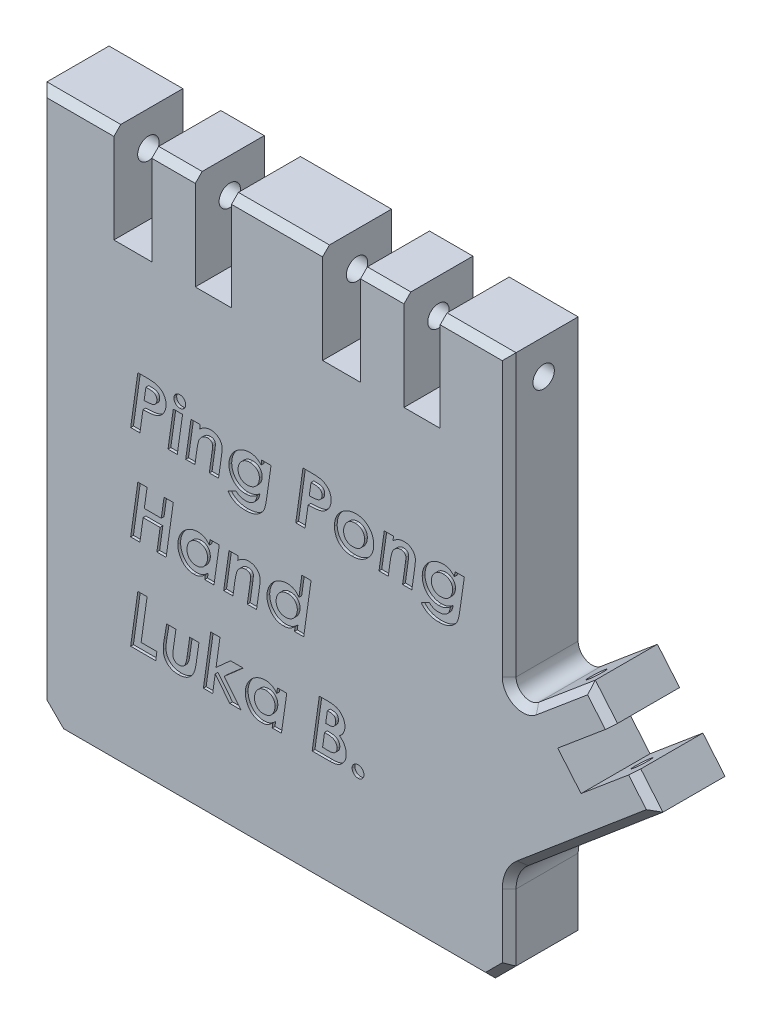
SolidWorks part; units mm, degrees
ref_plane "Plan de face" through (0, 0, 0) normal (0, 0, 1) x (1, 0, 0)
ref_plane "Plan de dessus" through (0, 0, 0) normal (0, 1, 0) x (1, 0, 0)
ref_plane "Plan de droite" through (0, 0, 0) normal (1, 0, 0) x (0, 0, -1)
sketch "Esquisse1" plane through (0, 0, 0) normal (0, 0, 1) x (1, 0, 0)
  line L1 (-34, -40) -> (34, -40)
  line L2 (-34, -40) -> (-34, 40)
  line L3 (-34, 40) -> (34, 40)
  line L4 (34, -40) -> (34, 40)
  line L5 (-34, -40) -> (34, 40) construction
  line L6 (-34, 40) -> (34, -40) construction
  point P0 (0, 0)
  dimension "D1" = 68
  dimension "D2" = 80
extrude "Boss.-Extru.1" add sketch "Esquisse1" along normal blind 10
sketch "Esquisse2" plane through (0, 0, 10) normal (0, 0, 1) x (1, 0, 0)
  line L0 (34, 40) -> (-34, 40) construction
  line L1 (18.75, 40) -> (24, 40)
  line L2 (18.75, 40) -> (18.75, 26)
  line L3 (18.75, 26) -> (24, 26)
  line L4 (24, 40) -> (24, 26)
  line L5 (34, -40) -> (34, 40) construction
  line L10 (-11.5, 40) -> (-6.25, 40)
  line L11 (-11.5, 40) -> (-11.5, 26)
  line L12 (-11.5, 26) -> (-6.25, 26)
  line L13 (-6.25, 40) -> (-6.25, 26)
  dimension "D1" = 5.25
  dimension "D2" = 10
  dimension "D3" = 14
  dimension "D4" = 25
extrude "Enlèv. mat.-Extru.1" cut sketch "Esquisse2" against normal blind 10
sketch "Esquisse3" plane through (34, 0, 0) normal (1, 0, 0) x (0, 0, -1)
  line L0 (-10, 40) -> (0, 40) construction
  circle A0 centre (-5, 35) radius 1.55
  point P4 (-5, 40)
  dimension "D1" = 3.1
  dimension "D2" = 5
extrude "Enlèv. mat.-Extru.2" cut sketch "Esquisse3" against normal through all
sketch "Esquisse8" plane through (0, 0, 10) normal (0, 0, 1) x (1, 0, 0)
  line L0 (34, -5) -> (45.4907, 4.6418)
  line L1 (34, -40) -> (34, 40) construction
  line L2 (45.4907, 4.6418) -> (48.7046, 0.8116)
  line L3 (48.7046, 0.8116) -> (41.0442, -5.6163)
  line L4 (41.0442, -5.6163) -> (44.4188, -9.638)
  line L5 (44.4188, -9.638) -> (52.0792, -3.2101)
  line L6 (52.0792, -3.2101) -> (55.2932, -7.0404)
  line L7 (55.2932, -7.0404) -> (34, -25)
  line L8 (34, -25) -> (34, -5)
  line L9 (-34, -40) -> (34, -40) construction
  dimension "D1" = 5.25
  dimension "D2" = 5
  dimension "D3" = 5
  dimension "D4" = 15
  dimension "D5" = 50
  dimension "D6" = 15
  dimension "D7" = 20
  dimension "D8" = 10
extrude "Boss.-Extru.3" add sketch "Esquisse8" against normal blind 10
sketch "Esquisse9" plane through (19.7239, -23.5061, 0) normal (0.6428, -0.766, 0) x (0.766, 0.6428, 0)
  line L0 (37.8316, 0) -> (37.8316, 10) construction
  circle A0 centre (32.8316, 5) radius 1.25
  point P4 (37.8316, 5)
  dimension "D1" = 2.5
  dimension "D2" = 5
extrude "Enlèv. mat.-Extru.6" cut sketch "Esquisse9" against normal blind 10 and the other way blind 10
fillet "Congé1" radius 2 1 edges at (34, -5, 5)
fillet "Congé2" radius 5 1 edges at (34, -25, 5)
sketch "Esquisse11" plane through (0, 0, 10) normal (0, 0, 1) x (1, 0, 0)
  line L0 (18.75, 40) -> (-6.25, 40) construction
  line L1 (6.95, 40) -> (12.45, 40)
  line L2 (6.95, 40) -> (6.95, 26)
  line L3 (6.95, 26) -> (12.45, 26)
  line L4 (12.45, 40) -> (12.45, 26)
  line L5 (-11.5, 40) -> (-34, 40) construction
  line L6 (-23.3, 40) -> (-17.8, 40)
  line L7 (-23.3, 40) -> (-23.3, 26)
  line L8 (-23.3, 26) -> (-17.8, 26)
  line L9 (-17.8, 40) -> (-17.8, 26)
  line L10 (-11.5, 26) -> (-6.25, 26) construction
  line L11 (-11.5, 40) -> (-11.5, 26) construction
  line L12 (18.75, 40) -> (18.75, 26) construction
  dimension "D1" = 6.3
  dimension "D2" = 5.5
  dimension "D3" = 6.3
extrude "Enlèv. mat.-Extru.8" cut sketch "Esquisse11" against normal blind 10
chamfer "Chanfrein1" distance 3 angle 45 2 edges at (-34, -40, 5) (34, -40, 5)
chamfer "Chanfrein2" distance 1 angle 45 17 edges at (-14.65, 40, 10) (0.35, 40, 10) (15.6, 40, 10) (53.6862, -5.1253, 10) (47.0976, 2.7267, 10) (41.3881, 1.1994, 10) (35.1548, -2.5236, 10) (29, 40, 10) (34, 19.6445, 10) (45.5348, -15.2711, 10) (34.4658, -25.2165, 10) (-28.65, 40, 10) (34, -32.1619, 10) (32.5, -38.5, 10) (0, -40, 10) (-32.5, -38.5, 10) (-34, 1.5, 10)
sketch "Esquisse12" plane through (0, 0, 10) normal (0, 0, 1) x (1, 0, 0)
  text T0 "<b><i>Ping Pong</i></b>\r\n<b><i>Hand</i></b>\r\n<b><i>Luka B.</i></b>" font "Century Gothic" height in points 28
extrude "Enlèv. mat.-Extru.9" cut sketch "Esquisse12" against normal blind 0.4
